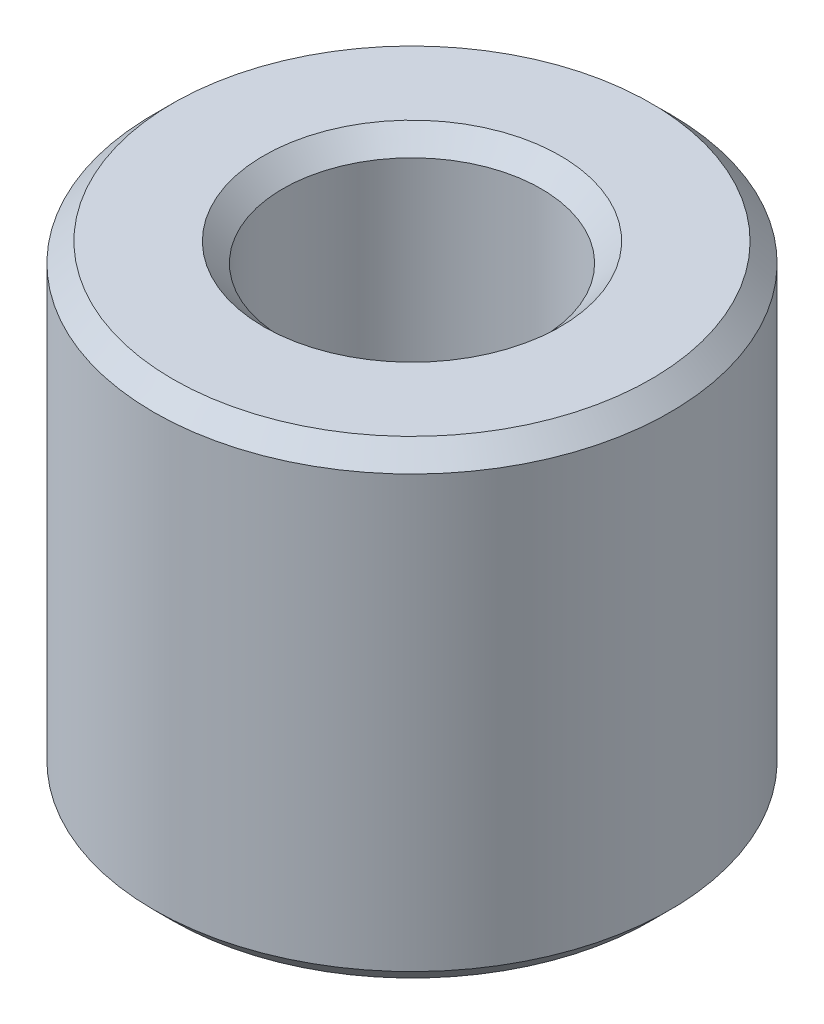
SolidWorks part; units mm, degrees
ref_plane "Front Plane" through (0, 0, 0) normal (0, 0, 1) x (1, 0, 0)
ref_plane "Top Plane" through (0, 0, 0) normal (0, 1, 0) x (1, 0, 0)
ref_plane "Right Plane" through (0, 0, 0) normal (1, 0, 0) x (0, 0, -1)
sketch "Sketch1" plane through (0, 0, 0) normal (0, 1, 0) x (1, 0, 0)
  circle A0 centre (0, 0) radius 37.5
  dimension "SLEEVE_OD" = 75
extrude "Boss-Extrude1" add sketch "Sketch1" along normal blind 68.1328
sketch "Sketch2" plane through (0, 0, 0) normal (0, 1, 0) x (1, 0, 0)
  circle A0 centre (0, 0) radius 18.7591
  dimension "BORE_D" = 37.5182
extrude "Cut-Extrude1" cut sketch "Sketch2" along normal through all
chamfer "Chamfer1" distance 2.7732 angle 45.022 4 edges at (0, 68.1328, 18.7591) (0, 0, 18.7591) (0, 0, 37.5) (0, 68.1328, 37.5) first distance on face at (0, 68.1328, 18.7591) first distance on face at (0, 0, 18.7591) first distance on face at (0, 68.1328, 37.5)
